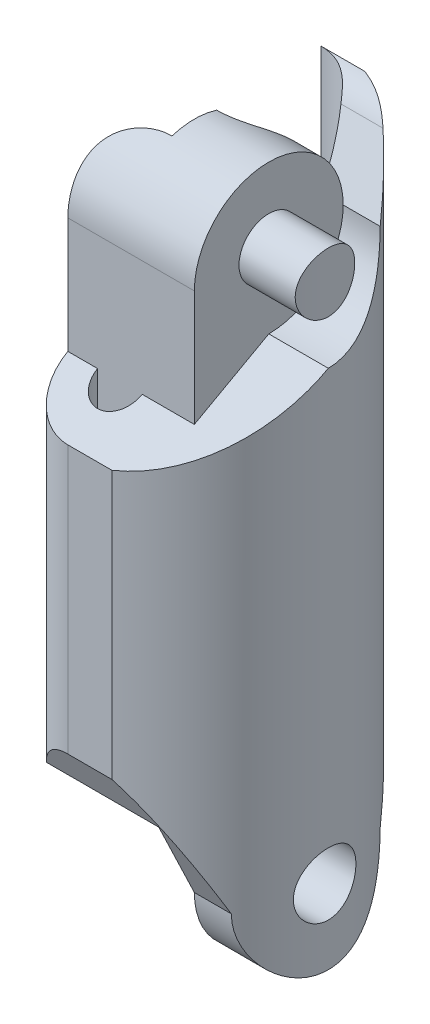
SolidWorks part; units mm, degrees
ref_plane "Front Plane" through (0, 0, 0) normal (0, 0, 1) x (1, 0, 0)
ref_plane "Top Plane" through (0, 0, 0) normal (0, 1, 0) x (1, 0, 0)
ref_plane "Right Plane" through (0, 0, 0) normal (1, 0, 0) x (0, 0, -1)
sketch "Sketch1" plane through (0, 0, 0) normal (0, 1, 0) x (1, 0, 0)
  line L0 (-2.958, 8.5) -> (2.958, 8.5)
  line L1 (-2.958, -8.5) -> (2.958, -8.5)
  arc A0 (-2.958, 8.5) -> (-2.958, -8.5) centre (0, 0) ccw
  arc A1 (2.958, 8.5) -> (2.958, -8.5) centre (0, 0) cw
  point P9 (-9, 0)
  point P10 (9, 0)
  dimension "D1" = 18
  dimension "D2" = 17
extrude "Boss-Extrude1" add sketch "Sketch1" along normal blind 45
sketch "Sketch2" plane through (0, 0, 0) normal (0, -1, 0) x (1, 0, 0)
  line L0 (-1.5, -5) -> (1.5, -5)
  line L1 (-1.5, 5) -> (1.5, 5)
  line L2 (0, -5) -> (0, 5) construction
  arc A2 (1.5, -5) -> (-1.5, -5) centre (0, -5) cw
  arc A3 (1.5, 5) -> (-1.5, 5) centre (0, 5) ccw
  point P5 (0, 0)
  point P10 (0, 0)
  dimension "D1" = 10
  dimension "D2" = 1.5
extrude "Cut-Extrude1" cut sketch "Sketch2" against normal blind 51.256
sketch "Sketch3" plane through (0, 0, -8.5) normal (0, 0, -1) x (-1, 0, 0)
  line L0 (5, 0) -> (5, 10)
  line L1 (5, 10) -> (-5, 10)
  line L2 (-5, 10) -> (-5, 0)
  line L3 (5, 0) -> (-5, 0)
  line L4 (-2.958, 0) -> (2.958, 0) construction
  point P10 (0, 0)
  dimension "D1" = 10
  dimension "D2" = 10
extrude "Cut-Extrude2" cut sketch "Sketch3" against normal up to surface (17 mm away) up to face at (0, 22.5, 8.5)
sketch "Sketch4" plane through (5, 0, 0) normal (-1, 0, 0) x (0, 0, 1)
  line L0 (-7.4833, 10) -> (-5, 5)
  line L1 (8.5, 12.3086) -> (5, 5)
  line L2 (7.4833, 0) -> (-7.4833, 0) construction
  line L3 (-7.4833, 10) -> (-9.8579, -1.8222)
  line L4 (-9.8579, -1.8222) -> (9.8579, -1.8222)
  line L6 (8.5, 45) -> (8.5, 10) construction
  line L7 (9.8579, -1.8222) -> (8.5, 12.3086)
  arc A0 (-5, 5) -> (5, 5) centre (0, 5) ccw
  circle A1 centre (0, 5) radius 2.1
  point P7 (0, 0)
  dimension "D1" = 4.2
  dimension "D2" = 5
  dimension "D3" = 12.0584
  dimension "D4" = 37.769
extrude "Cut-Extrude3" cut sketch "Sketch4" against normal mid plane 35
ref_plane "Plane1" through (-2.958, 0, 0) normal (-1, 0, 0) x (0, 0, 1)
sketch "Sketch6" plane through (-2.958, 0, 0) normal (-1, 0, 0) x (0, 0, 1)
  line L0 (8.5, 30.2956) -> (0, 35)
  line L1 (8.5, 45) -> (8.5, 12.3086) construction
  line L3 (8.5, 45) -> (-8.5, 45) construction
  line L4 (8.5, 30.2956) -> (18.3464, 50.6263)
  line L7 (-8.5, 45) -> (18.3464, 50.6263)
  line L8 (8.5, 45) -> (8.5, 12.3086) construction
  line L12 (-5, 40) -> (-6.926, 43.8779)
  line L13 (-5, 5) -> (-7.4833, 10) construction
  arc A0 (0, 35) -> (-5, 40) centre (0, 40) cw
  circle A1 centre (0, 40) radius 2
  arc A3 (-6.926, 43.8779) -> (-8.5, 45) centre (-8.7637, 42.9652) ccw
  dimension "D1" = 5
  dimension "D3" = 4
  dimension "D2" = 5
  dimension "D4" = 8.5
extrude "Cut-Extrude5" cut sketch "Sketch6" against normal blind 9.6 from surface starting at face at (5, 7.1, 0)
sketch "Sketch7" plane through (5, 0, 0) normal (1, 0, 0) x (0, 0, -1)
  line L3 (-8.5, 45) -> (-8.5, 12.3086) construction
  line L4 (-5, 40) -> (-5, 32.2327)
  line L5 (-7.4833, 45) -> (7.4833, 45) construction
  line L6 (-5, 32.2327) -> (-8.5, 30.2956)
  line L8 (0, 35) -> (-7.4833, 30.8583) construction
  line L10 (8.5, 45) -> (18.9606, 55.6302)
  line L11 (18.9606, 55.6302) -> (-10.6436, 58.7694)
  line L12 (-10.6436, 58.7694) -> (-8.5, 30.2956)
  line L14 (8.5, 45) -> (8.5, 10) construction
  line L15 (5, 40) -> (6.926, 43.8779)
  arc A0 (5, 40) -> (-5, 40) centre (0, 40) ccw
  arc A4 (6.926, 43.8779) -> (8.5, 45) centre (8.7637, 42.9652) cw
  dimension "D1" = 5
fillet "Fillet3" radius 1 4 edges at (0, 10, 6.5) (0, 10, 5) (0, 10, -6.5) (0, 10, -5)
extrude "Cut-Extrude6" cut sketch "Sketch6<3>" along normal blind 6.604 from surface starting at face at (-5, 2.9, 0)
sketch "Sketch6<3>" plane through (-2.958, 0, 0) normal (-1, 0, 0) x (0, 0, 1) same geometry as "Sketch6"
extrude "Cut-Extrude7" cut sketch "Sketch7" against normal blind 14.986
sketch "Sketch8" plane through (0, 10, 0) normal (0, -1, 0) x (1, 0, 0)
  line L0 (0, -1.5) -> (0, 1.5)
  line L1 (-2.958, -8.5) -> (2.958, -8.5) construction
  line L2 (2.958, 8.5) -> (-2.958, 8.5) construction
  line L3 (0, -8.5) -> (-22.0042, -13.9109)
  line L4 (-22.0042, -13.9109) -> (-22.0042, 31.798)
  line L5 (-22.0042, 31.798) -> (0, 8.5)
  arc A0 (0, -1.5) -> (0, -8.5) centre (0, -5) cw
  arc A1 (0, 1.5) -> (0, 8.5) centre (0, 5) cw
  arc A4 (-2.2913, -4) -> (2.2913, -4) centre (0, -5) ccw construction
  arc A5 (-0.7187, 7.3945) -> (-2.2913, 4) centre (0, 5) ccw construction
extrude "Cut-Extrude8" cut sketch "Sketch8" against normal mid plane 78.0815
sketch "Sketch9" plane through (0, 0, 0) normal (-1, 0, 0) x (0, 0, 1)
  line L0 (-1.5, 10) -> (1.5, 10) construction
  line L1 (0, 20) -> (0, 10) construction
  circle A0 centre (0, 20) radius 1.5
  dimension "D1" = 3
  dimension "D2" = 10
extrude "Cut-Extrude12" cut sketch "Sketch9" against normal blind 8.334
sketch "Sketch13" plane through (0, 0, 0) normal (-1, 0, 0) x (0, 0, 1)
  circle A0 centre (0, 20) radius 2
  dimension "D1" = 4
extrude "Cut-Extrude13" cut sketch "Sketch13" against normal mid plane 6.2
sketch "Sketch14" plane through (0, 0, 0) normal (-1, 0, 0) x (0, 0, 1)
  line L0 (-0.2053, 21.9894) -> (-0.2053, 23.4894)
  line L1 (-0.2053, 16.5106) -> (-0.2053, 18.0106)
  arc A0 (-0.2053, 21.9894) -> (-0.2053, 18.0106) centre (0, 20) ccw
  arc A1 (-0.2053, 23.4894) -> (-0.2053, 16.5106) centre (0, 20) ccw
  arc A2 (-1.5, 18.6771) -> (1.5, 18.6771) centre (0, 20) ccw construction
  arc A3 (1.5, 21.3229) -> (-1.5, 21.3229) centre (0, 20) ccw construction
  dimension "D1" = 1.5
extrude "Boss-Extrude3" add sketch "Sketch14" against normal blind 7.556
sketch "Sketch15" plane through (0, 0, 0) normal (-1, 0, 0) x (0, 0, 1)
  circle A0 centre (0, 40) radius 1.5
  circle A1 centre (0, 40) radius 2 construction
extrude "Cut-Extrude14" cut sketch "Sketch15" against normal blind 3
